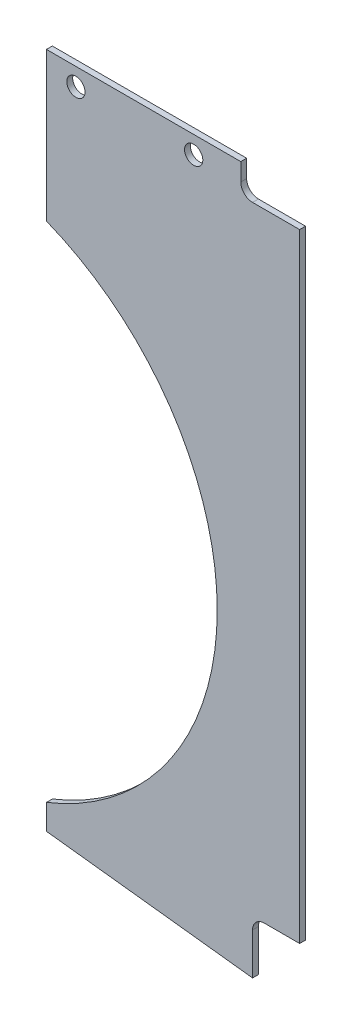
SolidWorks part; units mm, degrees
ref_plane "前视基准面" through (0, 0, 0) normal (0, 0, 1) x (1, 0, 0)
ref_plane "上视基准面" through (0, 0, 0) normal (0, 1, 0) x (1, 0, 0)
ref_plane "右视基准面" through (0, 0, 0) normal (1, 0, 0) x (0, 0, -1)
sketch "草图1" plane through (0, 0, 0) normal (0, 0, 1) x (1, 0, 0)
  line L0 (0, 0) -> (0, 115)
  line L1 (0, 115) -> (43, 115)
  line L2 (43, 115) -> (43, -5)
  line L3 (43, -5) -> (0, 0)
  line L4 (0, 112) -> (5, 112) construction
  line L5 (5, 112) -> (25, 112) construction
  circle A0 centre (5, 112) radius 1.55
  circle A1 centre (25, 112) radius 1.55
  dimension "D6" = 3.1
  dimension "D1" = 115
  dimension "D2" = 43
  dimension "D3" = 5
  dimension "D4" = 3
  dimension "D5" = 20
  dimension "D7" = 5
extrude "凸台-拉伸1" add sketch "草图1" along normal blind 1
sketch "草图2" plane through (0, 0, 1) normal (0, 0, 1) x (1, 0, 0)
  line L0 (-17, 47) -> (0, 47) construction
  line L1 (0, 115) -> (0, 0) construction
  line L3 (43, -5) -> (43, 115) construction
  circle A0 centre (-17, 47) radius 46
  dimension "D3" = 92
  dimension "D1" = 47
  dimension "D2" = 60
extrude "切除-拉伸1" cut sketch "草图2" against normal blind 2
sketch "草图3" plane through (0, 0, 1) normal (0, 0, 1) x (1, 0, 0)
  line L1 (43, -5) -> (35, -5)
  line L2 (43, -5) -> (43, 5)
  line L3 (43, 5) -> (35, 5)
  line L4 (35, -5) -> (35, 5)
  dimension "D1" = 10
  dimension "D2" = 8
extrude "切除-拉伸2" cut sketch "草图3" against normal blind 10
sketch "草图4" plane through (0, 0, 1) normal (0, 0, 1) x (1, 0, 0)
  line L1 (43, 115) -> (33, 115)
  line L2 (43, 115) -> (43, 110)
  line L3 (43, 110) -> (33, 110)
  line L4 (33, 115) -> (33, 110)
  line L5 (43, 115) -> (33, 110) construction
  line L6 (43, 110) -> (33, 115) construction
  point P4 (38, 112.5)
  dimension "D1" = 10
  dimension "D2" = 5
extrude "切除-拉伸3" cut sketch "草图4" against normal through all
fillet "圆角1" radius 2 2 edges at (33, 110, 0.5) (35, 5, 0.5)
